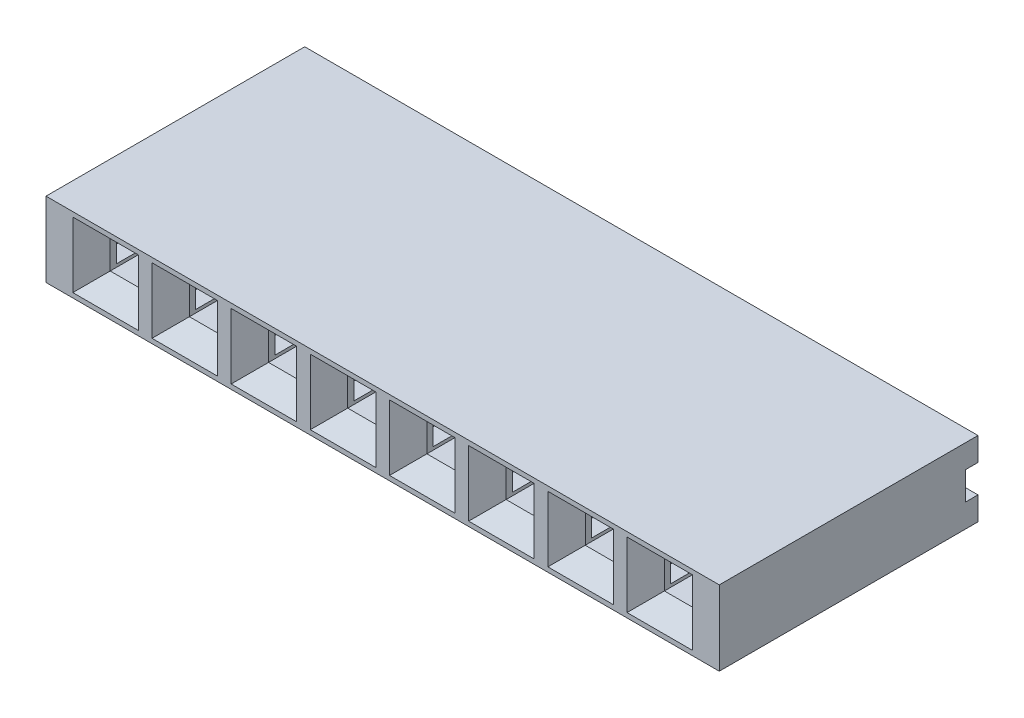
SolidWorks part; units mm, degrees
note: The reader was unsure of these and kept them because the rebuilt part matched: shared geometry of "Эскиз-БоковаяНакладка<2>".
other "Пластик"
ref_plane "Front Plane" through (0, 0, 0) normal (0, 0, 1) x (1, 0, 0)
ref_plane "Top Plane" through (0, 0, 0) normal (0, 1, 0) x (1, 0, 0)
ref_plane "Right Plane" through (0, 0, 0) normal (1, 0, 0) x (0, 0, -1)
sketch "Эскиз-ВнутреннееСечение" plane through (0, 0, 0) normal (0, 0, 1) x (1, 0, 0)
  line L0 (-1, 0.35) -> (-0.45, 0.35)
  line L1 (-1.27, -1.2) -> (1.27, -1.2)
  line L2 (-1.27, -1.2) -> (-1.27, 1.2)
  line L3 (-1.27, 1.2) -> (1.27, 1.2)
  line L4 (1.27, -1.2) -> (1.27, 1.2)
  line L5 (-1.27, -1.2) -> (1.27, 1.2) construction
  line L6 (-1.27, 1.2) -> (1.27, -1.2) construction
  line L8 (-1, -0.35) -> (-1, 0.35)
  line L9 (-0.45, 0.45) -> (0.45, 0.45)
  line L11 (0, 1.2) -> (0, -1.2) construction
  line L12 (0.45, 0.35) -> (0.45, 0.45)
  line L13 (-1.27, 0) -> (1.27, 0) construction
  line L14 (1, 0.35) -> (0.45, 0.35)
  line L15 (-0.45, 0.35) -> (-0.45, 0.45)
  line L16 (1, -0.35) -> (0.45, -0.35)
  line L17 (0.45, -0.35) -> (0.45, -0.45)
  line L18 (-0.45, -0.35) -> (-0.45, -0.45)
  line L19 (-1, -0.35) -> (-0.45, -0.35)
  line L20 (-0.45, -0.45) -> (0.45, -0.45)
  line L21 (1, -0.35) -> (1, 0.35)
  point P0 (0, 0)
  point P5 (0, 0)
  dimension "D1" = 2.4
  dimension "D2" = 2.54
  dimension "D3" = 1
  dimension "D4" = 0.35
  dimension "D5" = 0.1
  dimension "D7" = 0.55
extrude "Бобышка-ОтЦентраВверхВниз" add sketch "Эскиз-ВнутреннееСечение" against normal blind 0.4 and the other way blind 6.7 contours L8 L0 L15 L9 L12 L14 L21 L16 L17 L20 L18 L19
sketch "Эскиз-СамыйНиз" plane through (0, 0, -0.4) normal (0, 0, -1) x (-1, 0, 0)
  line L1 (1.27, 1.2) -> (1.27, -1.2) construction
  line L2 (-1.27, -1.2) -> (-1.27, 1.2) construction
  line L3 (0.45, -0.45) -> (-0.45, -0.45) construction
  line L4 (1.27, -1.2) -> (-1.27, -1.2)
  line L5 (1.27, -1.2) -> (1.27, -0.45)
  line L6 (1.27, -0.45) -> (-1.27, -0.45)
  line L7 (-1.27, -1.2) -> (-1.27, -0.45)
  line L9 (-1.27, 1.2) -> (1.27, 1.2)
  line L10 (-1.27, 1.2) -> (-1.27, 0.45)
  line L11 (-1.27, 0.45) -> (1.27, 0.45)
  line L12 (1.27, 1.2) -> (1.27, 0.45)
  line L13 (-0.45, 0.45) -> (0.45, 0.45) construction
extrude "Бобышка-СамыйНиз" add sketch "Эскиз-СамыйНиз" along normal blind 0.4
sketch "Эскиз-ВерхняяПеремычка" plane through (0, 0, 6.7) normal (0, 0, 1) x (1, 0, 0)
  line L1 (-1.27, 1.2) -> (1.27, 1.2)
  line L2 (-1.27, 1.2) -> (-1.27, -1.2)
  line L3 (-1.27, -1.2) -> (1.27, -1.2)
  line L4 (1.27, 1.2) -> (1.27, -1.2)
  line L5 (-0.45, -0.45) -> (0.45, -0.45)
  line L6 (-0.45, -0.45) -> (-0.45, 0.45)
  line L7 (-0.45, 0.45) -> (0.45, 0.45)
  line L8 (0.45, -0.45) -> (0.45, 0.45)
  line L9 (-0.45, -0.45) -> (0.45, 0.45) construction
  line L10 (-0.45, 0.45) -> (0.45, -0.45) construction
  point P4 (0, 0)
extrude "Бобышка-СамыйВерх" add sketch "Эскиз-ВерхняяПеремычка" along normal blind 0.8
chamfer "Фаска-СверхуВнутрь" distance 0.6 angle 45 4 edges at (0, -0.45, 7.5) (0.45, 0, 7.5) (0, 0.45, 7.5) (-0.45, 0, 7.5)
pattern_linear "Пластик_Массив" count 8 spacing 2.54 along (-1, 0, 0) of bodies 103
combine bodies "Соединить_Массив" operation type add bodies to combine 103 110 109 108 107 106 105 104
sketch "Эскиз-БоковаяНакладка" plane through (1.27, 0, 0) normal (1, 0, 0) x (0, 0, -1)
  line L1 (0.8, 1.2) -> (0.8, 0.45)
  line L2 (0.8, 0.45) -> (0.4, 0.45)
  line L3 (0.4, 0.45) -> (0.4, -0.45)
  line L4 (0.4, -0.45) -> (0.4, 0.45) construction
  line L5 (0.4, -0.45) -> (0.8, -0.45)
  line L6 (0.8, -0.45) -> (0.8, -1.2)
  line L7 (0.8, -1.2) -> (-7.5, -1.2)
  line L8 (-7.5, -1.2) -> (-7.5, 1.2)
  line L9 (-7.5, 1.2) -> (0.8, 1.2)
extrude "Бобышка-БоковаяНакладка1" add sketch "Эскиз-БоковаяНакладка" along normal blind 0.64 from surface at 0 starting at face at (1.27, 0, 1.375)
extrude "Бобышка-БоковаяНакладка2" add sketch "Эскиз-БоковаяНакладка<2>" against normal blind 0.64 from surface
sketch "Эскиз-БоковаяНакладка<2>" plane through (1.27, 0, 0) normal (1, 0, 0) x (0, 0, -1) same geometry as "Эскиз-БоковаяНакладка"
